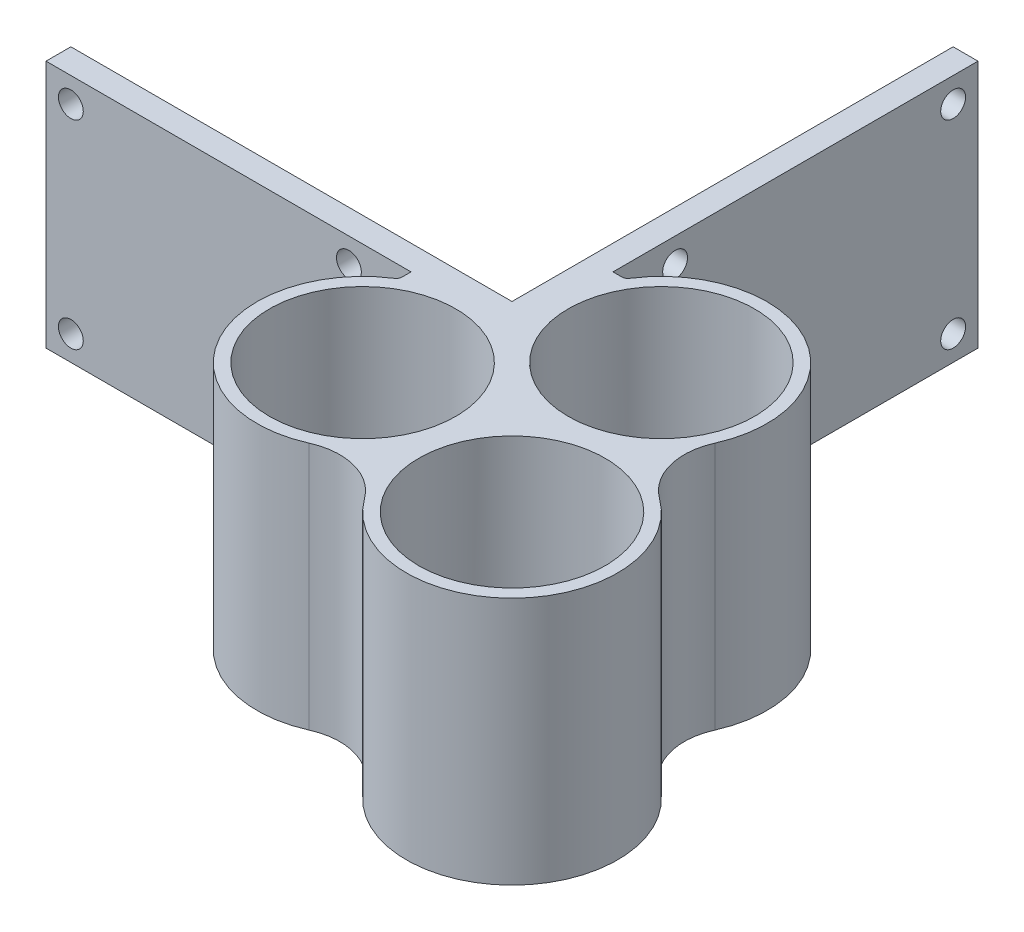
SolidWorks part; units mm, degrees
ref_plane "Front Plane" through (0, 0, 0) normal (0, 0, 1) x (1, 0, 0)
ref_plane "Top Plane" through (0, 0, 0) normal (0, 1, 0) x (1, 0, 0)
ref_plane "Right Plane" through (0, 0, 0) normal (1, 0, 0) x (0, 0, -1)
sketch "Sketch1" plane through (0, 0, 0) normal (0, 1, 0) x (1, 0, 0)
  line L1 (-15, -15) -> (15, -15)
  line L2 (-15, -15) -> (-15, 15)
  line L3 (-15, 15) -> (15, 15)
  line L4 (15, -15) -> (15, 15)
  line L5 (-15, -15) -> (15, 15) construction
  line L6 (-15, 15) -> (15, -15) construction
  point P0 (0, 0)
  dimension "D1" = 30
extrude "Boss-Extrude1" add sketch "Sketch1" along normal blind 80
sketch "Sketch2" plane through (0, 80, 0) normal (0, 1, 0) x (1, 0, 0)
  line L0 (-15, -15) -> (15, -15) construction
  line L1 (15, -15) -> (15, 15) construction
  circle A0 centre (9, -9) radius 6
  dimension "D1" = 12
extrude "Boss-Extrude2" add sketch "Sketch2" along normal blind 22
sketch "Sketch3" plane through (0, 80, 0) normal (0, 1, 0) x (1, 0, 0)
  line L2 (9, -15) -> (15, -15)
  line L4 (15, -15) -> (15, -9)
  circle A1 centre (9, -9) radius 6
  arc A4 (9, -15) -> (15, -9) centre (9, -9) ccw
  dimension "D1" = 0
extrude "Cut-Extrude1" cut sketch "Sketch3" against normal through all
sketch "Sketch4" plane through (0, 80, 0) normal (0, 1, 0) x (1, 0, 0)
  line L1 (-8.25, 11.25) -> (-1.75, 11.25) construction
  line L2 (-8.25, 11.25) -> (-8.25, 8.25)
  line L6 (-1.75, 1.75) -> (-11.25, 1.75)
  line L8 (-8.25, 8.25) -> (-11.25, 8.25)
  line L9 (-11.25, 1.75) -> (-11.25, 8.25) construction
  line L10 (-1.75, 11.25) -> (-1.75, 1.75)
  line L11 (-11.25, -1.25) -> (1.25, -1.25)
  line L12 (1.25, -1.25) -> (1.25, 11.25)
  line L13 (1.25, 11.25) -> (-1.75, 11.25) construction
  line L14 (-11.25, 1.75) -> (-11.25, -1.25) construction
  line L15 (-11.25, 8.25) -> (-11.25, 11.25) construction
  line L16 (-11.25, 11.25) -> (-8.25, 11.25) construction
  line L17 (1.25, 11.25) -> (1.25, 15)
  line L18 (15, 15) -> (-15, 15) construction
  line L19 (1.25, 15) -> (-1.75, 15)
  line L20 (-1.75, 15) -> (-1.75, 11.25)
  line L21 (-8.25, 11.25) -> (-8.25, 15)
  line L22 (-8.25, 15) -> (-11.25, 15)
  line L23 (-11.25, 15) -> (-11.25, 11.25)
  line L24 (-11.25, 11.25) -> (-15, 11.25)
  line L25 (-15, 15) -> (-15, -15) construction
  line L26 (-15, 11.25) -> (-15, 8.25)
  line L27 (-15, 8.25) -> (-11.25, 8.25)
  line L28 (-11.25, 1.75) -> (-15, 1.75)
  line L29 (-15, 1.75) -> (-15, -1.25)
  line L30 (-15, -1.25) -> (-11.25, -1.25)
  dimension "D1" = 6.5
  dimension "D2" = 3
  dimension "D3" = 3.75
extrude "Boss-Extrude3" add sketch "Sketch4" along normal blind 100
sketch "Sketch6" plane through (0, 0, 0) normal (0, -1, 0) x (1, 0, 0)
  line L1 (15, -15) -> (7, -15)
  line L2 (15, -15) -> (15, -105.5)
  line L3 (15, -105.5) -> (13, -105.5)
  line L4 (7, -15) -> (7, -99.5)
  arc A1 (7, -99.5) -> (13, -105.5) centre (7, -105.5) ccw
  dimension "D3" = 12
  dimension "D1" = 90.5
  dimension "D2" = 8
extrude "Boss-Extrude5" add sketch "Sketch6" against normal blind 2
sketch "Sketch7" plane through (0, 2, 0) normal (0, 1, 0) x (1, 0, 0)
  line L0 (7, 109.5) -> (7, 111.5) construction
  line L1 (9, 111.1569) -> (9, 108.9641)
  line L2 (5, 111.1569) -> (5, 108.9641)
  line L3 (7, 101.5) -> (7, 99.5) construction
  line L4 (15, 105.5) -> (13, 105.5)
  line L5 (15, 105.5) -> (15, 15)
  line L6 (15, 15) -> (7, 15)
  line L7 (7, 15) -> (7, 99.5) construction
  line L8 (15, 15) -> (1.25, 15) construction
  line L9 (7, 15) -> (7, 99.5)
  arc A0 (5, 111.1569) -> (7, 99.5) centre (7, 105.5) ccw
  arc A1 (13, 105.5) -> (7, 99.5) centre (7, 105.5) ccw construction
  arc A2 (5, 108.9641) -> (9, 108.9641) centre (7, 105.5) ccw
  arc A3 (13, 105.5) -> (9, 111.1569) centre (7, 105.5) ccw
  dimension "D1" = 2
  dimension "D2" = 2
extrude "Boss-Extrude6" add sketch "Sketch7" along normal offset from surface (23 mm away) 25 up to face at (3.75, 0, -38.4375)
sketch "Sketch9" plane through (0, 0, 0) normal (0, -1, 0) x (1, 0, 0)
  line L0 (15, -15) -> (7, -15) construction
  line L1 (-15, 15) -> (-132.175, 15) construction
  line L2 (-15, 15) -> (-15, 7)
  line L3 (-15, 7) -> (-126.175, 7) construction
  line L4 (-132.175, 15) -> (-132.175, 13.1746) construction
  line L5 (-136.05, 7) -> (-136.175, 7) construction
  line L6 (-128.175, 7) -> (-126.175, 7) construction
  line L7 (-126.175, 9) -> (-128.856, 9) construction
  line L8 (7, -109.5) -> (7, -111.5) construction
  line L9 (9, -111.1569) -> (5, -111.1569) construction
  line L10 (-126.175, 5) -> (-128.856, 5) construction
  line L11 (-126.175, 9) -> (-126.175, 5) construction
  line L12 (-128.7978, 8.9) -> (-126.3, 8.9)
  line L13 (-128.7978, 5.1) -> (-126.175, 5.1) construction
  line L14 (-126.175, 5.1) -> (-126.175, 7) construction
  line L15 (-126.175, 8.9) -> (-126.3, 8.9) construction
  line L16 (-132.05, 15) -> (-132.05, 13.1733)
  line L17 (-132.05, 14.0867) -> (-132.175, 14.0873) construction
  line L18 (-132.05, 15) -> (-15, 15)
  line L19 (-126.175, 5.1) -> (-126.175, 7) construction
  line L20 (-15, 7) -> (-126.175, 7)
  line L21 (-126.4838, 5.1) -> (-128.7978, 5.1)
  circle A0 centre (-132.175, 7) radius 4 construction
  arc A1 (9, -108.9641) -> (5, -108.9641) centre (7, -105.5) ccw construction
  arc A2 (-128.7978, 8.9) -> (-128.7978, 5.1) centre (-132.175, 7) ccw
  arc A4 (-126.3, 8.9) -> (-132.175, 13.1746) centre (-132.175, 7) ccw construction
  arc A6 (-126.3, 8.9) -> (-132.05, 13.1733) centre (-132.175, 7) ccw
  arc A7 (-126.4838, 5.1) -> (-126.175, 7) centre (-132.175, 7) ccw
  arc A8 (7, -99.5) -> (5, -111.1569) centre (7, -105.5) ccw construction
  dimension "D1" = 117.175
  dimension "D2" = 0.125
  dimension "D3" = 1.9
extrude "Boss-Extrude7" add sketch "Sketch9" against normal blind 25
fillet "Fillet1" radius 2 1 edges at (-126.175, 12.5, 7)
sketch "Sketch11" plane through (0, 0, 0) normal (0, -1, 0) x (1, 0, 0)
  line L0 (-126.3, 8.9) -> (-126.425, 8.9) construction
  line L2 (-126.3, 8.9) -> (-128.7978, 8.9) construction
  line L3 (-136.05, 7) -> (-136.175, 7) construction
  circle A0 centre (-132.175, 7) radius 6.0558
  arc A5 (-128.7978, 8.9) -> (-128.7978, 5.1) centre (-132.175, 7) ccw construction
extrude "Cut-Extrude2" cut sketch "Sketch11" against normal offset from surface (2.125 mm away) 0.125 up to face at (7, 2, -108.2802) offset beyond the face yes
sketch "Sketch12" plane through (-15, 0, 0) normal (-1, 0, 0) x (0, 0, 1)
  line L1 (-15, 77) -> (-1.75, 77)
  line L2 (-15, 77) -> (-15, 68.5)
  line L3 (-15, 68.5) -> (-1.75, 68.5)
  line L4 (-1.75, 77) -> (-1.75, 68.5)
  line L6 (-15, 80) -> (-15, 0) construction
  line L7 (-15, 80) -> (-1.75, 80) construction
  line L9 (-1.75, 180) -> (-1.75, 80) construction
  dimension "D1" = 8.5
  dimension "D2" = 3
extrude "Cut-Extrude4" cut sketch "Sketch12" against normal up to surface (13.25 mm away) up to face at (-1.75, 130, -8.375)
sketch "Sketch14" plane through (0, 0, 15) normal (0, 0, 1) x (1, 0, 0)
  line L0 (15, 0) -> (-136.05, 0) construction
  line L1 (-136.05, 25) -> (-136.05, 2.125) construction
  line L2 (-132.05, 0) -> (9, 0) construction
sketch "Sketch15" plane through (0, 80, 0) normal (0, 1, 0) x (1, 0, 0)
  line L4 (-11.25, 11.25) -> (-11.25, 15)
  line L5 (-11.25, 15) -> (-15, 15)
  line L6 (-15, 15) -> (-15, 11.25)
  line L7 (-15, 11.25) -> (-11.25, 11.25)
  line L8 (-11.25, 11.25) -> (-11.25, 15)
  line L9 (-11.25, 15) -> (-15, 15)
  line L10 (-15, 15) -> (-15, 11.25)
  line L11 (-15, 11.25) -> (-11.25, 11.25)
  dimension "D1" = 0
extrude "Cut-Extrude5" cut sketch "Sketch15" against normal up to next
fillet "Fillet2" radius 1 5 edges at (1.25, 130, -15) (-11.25, 128.5, -15) (-11.25, 128.5, -11.25) (-15, 128.5, -11.25) (-15, 130, 1.25)
sketch "Sketch16" plane through (0, 80, 0) normal (0, 1, 0) x (1, 0, 0)
  circle A0 centre (9, -9) radius 6
  circle A1 centre (9, -9) radius 6 construction
extrude "Cut-Extrude7" cut sketch "Sketch16" along normal up to next
sketch "Sketch17" plane through (0, 180, 0) normal (0, 1, 0) x (1, 0, 0)
  line L0 (18.7916, -9.75) -> (18.7916, -11.75) construction
  line L1 (1.25, 5.25) -> (3.7916, 5.25) construction
  line L2 (1.25, -1.25) -> (1.25, 14) construction
  line L3 (-5.25, -3.7916) -> (-5.25, -1.25) construction
  line L4 (-14, -1.25) -> (1.25, -1.25) construction
  line L6 (-5.25, -1.25) -> (1.25, -1.25) construction
  line L7 (1.25, -1.25) -> (1.25, 5.25) construction
  line L8 (-14, -1.25) -> (-14, -4.2164)
  line L9 (1.25, 14) -> (4.2164, 14)
  line L10 (-14, -1.25) -> (1.25, -1.25)
  line L11 (1.25, -1.25) -> (1.25, 14)
  circle A0 centre (18.7916, 5.25) radius 15
  circle A1 centre (-5.25, -18.7916) radius 15
  arc A2 (20.5619, -11.6576) -> (4.2164, 14) centre (18.7916, 5.25) ccw
  arc A3 (-14, -4.2164) -> (11.6576, -20.5619) centre (-5.25, -18.7916) ccw
  arc A4 (11.6576, -20.5619) -> (20.5619, -11.6576) centre (21.6032, -21.6032) cw
  dimension "D1" = 30
  dimension "D3" = 10
  dimension "D2" = 2
  dimension "D4" = 6.5
extrude "Boss-Extrude8" add sketch "Sketch17" against normal blind 40
fillet "Fillet3" radius 1 4 edges at (4.2164, 160, -14) (1.25, 160, -14) (-14, 160, 1.25) (-14, 160, 4.2164)
sketch "Sketch18" plane through (0, 140, 0) normal (0, -1, 0) x (1, 0, 0)
  circle A0 centre (-5.25, 18.7916) radius 15 construction
  circle A1 centre (-5.25, 18.7916) radius 15
  circle A2 centre (-5.25, 18.7916) radius 7.5
  dimension "D1" = 15
extrude "Boss-Extrude9" add sketch "Sketch18" against normal blind 2
sketch "Sketch19" plane through (0, 140, 0) normal (0, -1, 0) x (1, 0, 0)
  line L0 (-5.25, 26.2916) -> (-5.25, 11.2916) construction
  circle A0 centre (-5.25, 18.7916) radius 7.5 construction
ref_plane "Plane1" through (-5.25, 0, 0) normal (-1, 0, 0) x (0, 0, -1)
sketch "Sketch21" plane through (-5.25, 0, 0) normal (-1, 0, 0) x (0, 0, -1)
  line L0 (-11.2916, -142) -> (-3.7916, -154.5)
  line L1 (-26.2916, -142) -> (-11.2916, -142) construction
  line L2 (-3.7916, -154.5) -> (-3.7916, -142)
  line L3 (-33.7916, -142) -> (-3.7916, -142) construction
  line L4 (-3.7916, -142) -> (-11.2916, -142)
  line L5 (-18.7916, -1065) -> (-18.7916, 48935) construction
  line L6 (-26.2916, -140) -> (-11.2916, -140) construction
  point P14 (-18.7916, -140)
  dimension "D1" = 12.5
revolve "Revolve1" add sketch "Sketch21" angle 360 about L5
ref_plane "Plane2" through (0, 0, 0) normal (0.7071, 0, -0.7071) x (-0.7071, 0, -0.7071)
mirror "Mirror1" about plane through (0, 0, 0) normal (0.7071, 0, -0.7071) of "Revolve1", "Boss-Extrude9"
sketch "Sketch22" plane through (0, 140, 0) normal (0, -1, 0) x (1, 0, 0)
  circle A0 centre (0, 0) radius 209.0164
extrude "Cut-Extrude8" cut sketch "Sketch22" along normal through all
sketch "Sketch23" plane through (0, 180, 0) normal (0, 1, 0) x (1, 0, 0)
  line L1 (-26.7546, 5.072) -> (-4.6842, 5.072)
  line L2 (-26.7546, 5.072) -> (-26.7546, 21.2842)
  line L3 (-26.7546, 21.2842) -> (-4.6842, 21.2842)
  line L4 (-4.6842, 5.072) -> (-4.6842, 21.2842)
extrude "Cut-Extrude9" cut sketch "Sketch23" against normal through all
sketch "Sketch24" plane through (0, 180, 0) normal (0, 1, 0) x (1, 0, 0)
  line L0 (-1.75, 1.75) -> (0, 0) construction
  line L1 (0, 0) -> (39.6123, -39.6123) construction
  line L2 (-5.25, -18.7916) -> (18.7916, 5.25) construction
  line L3 (18.7916, 5.25) -> (27.5915, -27.5915) construction
  line L4 (27.5915, -27.5915) -> (-5.25, -18.7916) construction
  line L5 (-20.25, -18.7916) -> (-22.25, -18.7916) construction
  line L6 (42.5915, -27.5915) -> (44.5915, -27.5915) construction
  circle A0 centre (27.5915, -27.5915) radius 15
  circle A1 centre (18.7916, 5.25) radius 15 construction
  circle A2 centre (18.7916, 5.25) radius 15 construction
  arc A3 (13.8342, -37.5784) -> (37.5784, -13.8342) centre (27.5915, -27.5915) ccw
  circle A4 centre (-5.25, -18.7916) radius 15 construction
  arc A5 (-14.4583, -4.5015) -> (11.6576, -20.5619) centre (-5.25, -18.7916) ccw construction
  arc A6 (13.8342, -37.5784) -> (1.6707, -34.3192) centre (5.7417, -43.453) ccw
  arc A7 (37.5784, -13.8342) -> (34.3192, -1.6707) centre (43.453, -5.7417) cw
  arc A8 (20.5619, -11.6576) -> (11.6576, -20.5619) centre (21.6032, -21.6032) ccw construction
  arc A9 (20.5619, -11.6576) -> (4.5015, 14.4583) centre (18.7916, 5.25) ccw construction
  arc A10 (20.5619, -11.6576) -> (34.3192, -1.6707) centre (18.7916, 5.25) ccw
  arc A11 (20.5619, -11.6576) -> (11.6576, -20.5619) centre (21.6032, -21.6032) ccw
  arc A12 (1.6707, -34.3192) -> (11.6576, -20.5619) centre (-5.25, -18.7916) ccw
extrude "Boss-Extrude10" add sketch "Sketch24" against normal up to surface (40 mm away) up to face at (-2.677, 140, -2.677)
sketch "Sketch25" plane through (0, 140, 0) normal (0, -1, 0) x (1, 0, 0)
  circle A0 centre (27.5915, 27.5915) radius 15 construction
  circle A1 centre (27.5915, 27.5915) radius 15
  circle A2 centre (27.5915, 27.5915) radius 7.5
  circle A3 centre (-5.25, 18.7916) radius 7.5 construction
  point P6 (0, 0)
extrude "Boss-Extrude11" add sketch "Sketch25" against normal blind 2
ref_plane "Plane3" through (0, 0, 0) normal (0.7071, 0, -0.7071) x (-0.7071, 0, -0.7071)
sketch "Sketch26" plane through (0, 0, 0) normal (0.7071, 0, -0.7071) x (-0.7071, 0, -0.7071)
  line L0 (-39.0202, 126.9954) -> (-39.0202, 195.0175) construction
  line L2 (-24.0202, 142) -> (-24.0202, 154.5)
  line L3 (-24.0202, 154.5) -> (-31.5202, 142)
  line L4 (-31.5202, 142) -> (-24.0202, 142)
  line L5 (-24.0202, 142) -> (-54.0202, 142) construction
  line L7 (-24.0202, 142) -> (-24.0202, 180) construction
  line L8 (-31.5202, 142) -> (-46.5202, 142) construction
  point P8 (-24.0202, 142)
  point P10 (0, 0)
  point P12 (-30.0101, 142)
  dimension "D1" = 12.5
revolve "Revolve2" add sketch "Sketch26" angle 360 about L0
sketch "Sketch27" plane through (0, 180, 0) normal (0, 1, 0) x (1, 0, 0)
  line L0 (2.25, 14) -> (2.25, -2.25) construction
  line L1 (2.25, -2.25) -> (-14, -2.25) construction
  line L2 (2.25, -2.25) -> (2.25, 72.75)
  line L3 (2.25, 72.75) -> (-1.75, 72.75)
  line L4 (-1.75, 72.75) -> (-1.75, 1.75)
  line L5 (-1.75, 15) -> (-1.75, 1.75) construction
  line L6 (-1.75, 1.75) -> (-72.75, 1.75)
  line L7 (-72.75, 1.75) -> (-72.75, -2.25)
  line L8 (-72.75, -2.25) -> (2.25, -2.25)
  line L9 (-1.75, 1.75) -> (-15, 1.75) construction
  line L10 (3.6609, 14) -> (1.9821, 14) construction
  line L11 (-14, -1.9821) -> (-14, -3.6609) construction
  point P14 (0, 0)
  point P15 (0, 0)
  point P16 (0, 0)
  point P17 (-35.0796, 1.75)
  point P18 (2.25, 14)
  point P21 (-14, -2.25)
  dimension "D1" = 4
  dimension "D2" = 75
extrude "Boss-Extrude12" add sketch "Sketch27" against normal up to surface (40 mm away) up to face at (0.8594, 140, 0.8594)
sketch "Sketch29" plane through (0, 0, 2.25) normal (0, 0, 1) x (1, 0, 0)
  line L0 (-72.75, 140) -> (-14, 140) construction
  line L1 (-14, 140) -> (-14, 180) construction
  line L2 (-72.75, 160) -> (-8.9096, 160) construction
  line L3 (-72.75, 140) -> (-72.75, 180) construction
  circle A0 centre (-24, 144) radius 2
  circle A1 centre (-24, 176) radius 2
  circle A2 centre (-68.75, 144) radius 2
  circle A3 centre (-68.75, 176) radius 2
  point P14 (0, 0)
  dimension "D1" = 4
  dimension "D2" = 4
  dimension "D3" = 10
  dimension "D4" = 4
extrude "Cut-Extrude10" cut sketch "Sketch29" against normal through all
sketch "Sketch30" plane through (0, 0, -1.75) normal (0, 0, -1) x (-1, 0, 0)
  line L0 (17.16, 148) -> (26.52, 148) construction
  line L1 (32.57, 148) -> (41.93, 148) construction
  line L2 (47.98, 148) -> (57.34, 148) construction
  line L3 (72.75, 140) -> (1.75, 140) construction
  line L4 (72.75, 160) -> (1.75, 160) construction
  line L5 (11.11, 148) -> (1.75, 148) construction
  line L6 (1.75, 180) -> (1.75, 140) construction
  line L7 (63.39, 148) -> (72.75, 148) construction
  line L8 (72.75, 140) -> (72.75, 180) construction
  line L9 (63.39, 172) -> (72.75, 172) construction
  line L10 (11.11, 172) -> (1.75, 172) construction
  line L11 (47.98, 172) -> (57.34, 172) construction
  line L12 (32.57, 172) -> (41.93, 172) construction
  line L13 (17.16, 172) -> (26.52, 172) construction
  circle A0 centre (14.135, 148) radius 3.025
  circle A1 centre (29.545, 148) radius 3.025
  circle A2 centre (44.955, 148) radius 3.025
  circle A3 centre (60.365, 148) radius 3.025
  circle A4 centre (60.365, 172) radius 3.025
  circle A5 centre (44.955, 172) radius 3.025
  circle A6 centre (29.545, 172) radius 3.025
  circle A7 centre (14.135, 172) radius 3.025
  dimension "D1" = 6.05
  dimension "D2" = 8
extrude "Cut-Extrude11" cut sketch "Sketch30" against normal blind 2.1
mirror "Mirror2" about plane through (0, 0, 0) normal (0.7071, 0, -0.7071) of "Cut-Extrude11", "Cut-Extrude10"
